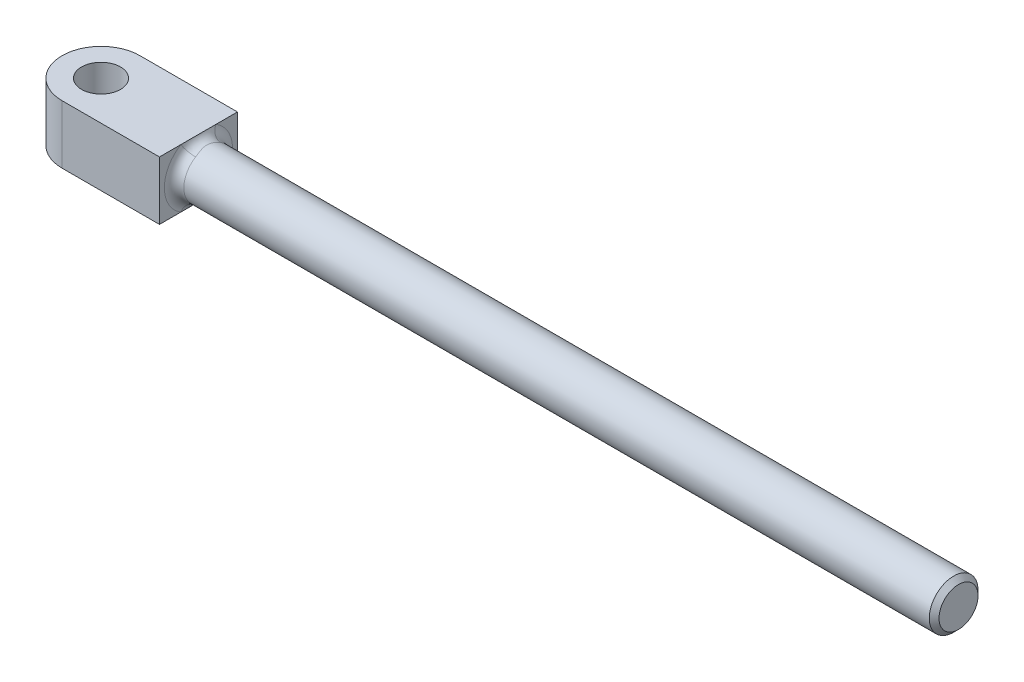
SolidWorks part; units mm, degrees
material "Alloy Steel"
ref_plane "Front Plane" through (0, 0, 0) normal (0, 0, 1) x (1, 0, 0)
ref_plane "Top Plane" through (0, 0, 0) normal (0, 1, 0) x (1, 0, 0)
ref_plane "Right Plane" through (0, 0, 0) normal (1, 0, 0) x (0, 0, -1)
sketch "Sketch2" plane through (0, 0, 0) normal (0, 1, 0) x (1, 0, 0)
  line L1 (-5, 4) -> (5, 4)
  line L3 (-5, -4) -> (5, -4)
  line L4 (5, 4) -> (5, -4)
  line L5 (-5, 4) -> (5, -4) construction
  line L6 (-5, -4) -> (5, 4) construction
  arc A0 (-5, 4) -> (-5, -4) centre (-5, 0) ccw
  circle A1 centre (-5, 0) radius 2
  point P0 (0, 0)
  dimension "D3" = 4
  dimension "D5" = 4
  dimension "D1" = 10
  dimension "D2" = 8
  dimension "D4" = 5
extrude "Boss-Extrude1" add sketch "Sketch2" along normal mid plane 6
sketch "Sketch3" plane through (5, 0, 0) normal (1, 0, 0) x (0, 0, -1)
  circle A0 centre (0, 0) radius 2.5
  dimension "D1" = 5
extrude "Boss-Extrude2" add sketch "Sketch3" along normal blind 78
cosmetic thread "Cosmetic Thread2" parameters "D1"=14, "D2"=4.11
fillet "Fillet1" radius 1 1 edges at (5, 0, -2.5)
chamfer "Chamfer1" distance 0.5 angle 45 1 edges at (83, 0, -2.5)
